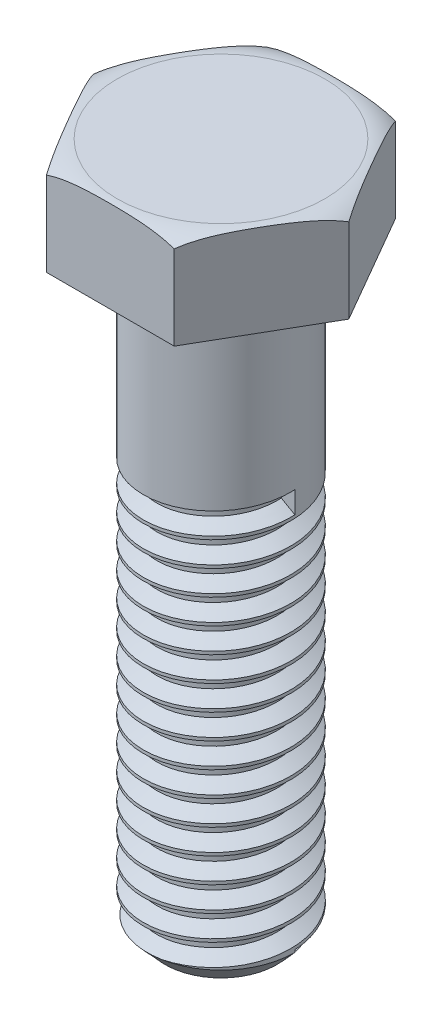
SolidWorks part; units mm, degrees
ref_plane "Front Plane" through (0, 0, 0) normal (0, 0, 1) x (1, 0, 0)
ref_plane "Top Plane" through (0, 0, 0) normal (0, 1, 0) x (1, 0, 0)
ref_plane "Right Plane" through (0, 0, 0) normal (1, 0, 0) x (0, 0, -1)
sketch "Sketch1" plane through (0, 0, 0) normal (0, 1, 0) x (1, 0, 0)
  line L1 (8.1462, 0) -> (4.0731, 7.0549)
  line L2 (4.0731, 7.0549) -> (-4.0731, 7.0548)
  line L3 (-4.0731, 7.0548) -> (-8.1462, 0)
  line L4 (-8.1462, 0) -> (-4.0731, -7.0549)
  line L5 (-4.0731, -7.0549) -> (4.0731, -7.0548)
  line L6 (4.0731, -7.0548) -> (8.1462, 0)
  circle A0 centre (0, 0) radius 7.0549 construction
  dimension "D1" = 14.1097
extrude "Boss-Extrude1" add sketch "Sketch1" against normal blind 43.8023
sketch "Sketch2" plane through (0, -43.8023, 0) normal (0, -1, 0) x (1, 0, 0)
  line L0 (-8.1462, 0) -> (-4.0731, 7.0549) construction
  line L1 (-8.1462, 0) -> (-4.0731, 7.0549)
  line L2 (-4.0731, -7.0548) -> (-8.1462, 0) construction
  line L3 (4.0731, -7.0549) -> (-4.0731, -7.0548) construction
  line L4 (8.1462, 0) -> (4.0731, -7.0549) construction
  line L5 (4.0731, 7.0548) -> (8.1462, 0) construction
  line L6 (-4.0731, 7.0549) -> (4.0731, 7.0548) construction
  line L7 (-4.0731, -7.0548) -> (-8.1462, 0)
  line L8 (4.0731, -7.0549) -> (-4.0731, -7.0548)
  line L9 (8.1462, 0) -> (4.0731, -7.0549)
  line L10 (4.0731, 7.0548) -> (8.1462, 0)
  line L11 (-4.0731, 7.0549) -> (4.0731, 7.0548)
  circle A0 centre (0, 0) radius 4.7053
  dimension "D1" = 9.4107
extrude "Cut-Extrude1" cut sketch "Sketch2" against normal blind 37.9222
thread "Thread1" pitch 1.5875 method cut profile "Thread Profile1" start angle 0, offset 0, length 25.4, pitch 1.5875, diameter 9.4107
ref_plane "Plane1" through (4.7054, -43.8023, 0) normal (0, 0, 1) x (1, 0, 0)
sketch "Thread Profile1" plane through (4.7054, -43.8023, 0) normal (0, 0, 1) x (1, 0, 0)
  line L0 (0, 0) -> (0, 1.5875) construction
  line L11 (0, 0) -> (0, 1.3891)
  line L12 (0, 1.3891) -> (-0.8593, 0.893)
  line L13 (-0.8593, 0.893) -> (-0.8593, 0.4961)
  line L15 (-0.8593, 0.4961) -> (0, 0)
  line L17 (-0.8593, 0.6945) -> (0, 0.6945) construction
  point P2 (0, 0)
  dimension "Pitch" = 1.5875
  dimension "Profile_Angle" = 60
  dimension "Profile_Land" = 0.3969
  dimension "Profile_Height" = 0.8593
sketch "Sketch8" plane through (0, 0, 0) normal (0, 0, 1) x (1, 0, 0)
  line L0 (-0.1235, -43.8023) -> (8.5552, -43.8023) construction
  line L1 (-4.7054, -43.8023) -> (4.7054, -43.8023) construction
  line L2 (0, -44.3948) -> (0, -41.2226) construction
  line L3 (3.0373, -43.8023) -> (2.8966, -43.6616)
  line L7 (3.5696, -43.8023) -> (5.2966, -41.9236)
  line L8 (5.2966, -41.9236) -> (5.2966, -43.8023)
  line L9 (5.2966, -43.8023) -> (3.5696, -43.8023)
  line L11 (0, -43.6616) -> (0, -43.8023)
  line L12 (0, -43.8023) -> (3.0373, -43.8023)
  line L13 (0, -43.6616) -> (2.8966, -43.6616)
  spline S0 degree 2 poles (4.7054, -42.4132) (4.7054, -42.314) (3.3272, -42.2148) (1.949, -42.1156) (0, -42.0164) (-1.949, -41.9171) (-3.3272, -41.8179) (-4.7054, -41.7187) (-4.7054, -41.6195) (-4.7054, -41.5203) (-3.3272, -41.4211) (-1.949, -41.3218) (0, -41.2226) (1.949, -41.1234) (3.3272, -41.0242) (4.7054, -40.925) (4.7054, -40.8257) (4.7054, -40.7265) (3.3272, -40.6273) (1.949, -40.5281) (0, -40.4289) (-1.949, -40.3296) (-3.3272, -40.2304) (-4.7054, -40.1312) (-4.7054, -40.032) (-4.7054, -39.9328) (-3.3272, -39.8336) (-1.949, -39.7343) (0, -39.6351) (1.949, -39.5359) (3.3272, -39.4367) (4.7054, -39.3375) (4.7054, -39.2382) (4.7054, -39.139) (3.3272, -39.0398) (1.949, -38.9406) (0, -38.8414) (-1.949, -38.7421) (-3.3272, -38.6429) (-4.7054, -38.5437) (-4.7054, -38.4445) (-4.7054, -38.3453) (-3.3272, -38.2461) (-1.949, -38.1468) (0, -38.0476) (1.949, -37.9484) (3.3272, -37.8492) (4.7054, -37.75) (4.7054, -37.6507) (4.7054, -37.5515) (3.3272, -37.4523) (1.949, -37.3531) (0, -37.2539) (-1.949, -37.1546) (-3.3272, -37.0554) (-4.7054, -36.9562) (-4.7054, -36.857) (-4.7054, -36.7578) (-3.3272, -36.6586) (-1.949, -36.5593) (0, -36.4601) (1.949, -36.3609) (3.3272, -36.2617) (4.7054, -36.1625) (4.7054, -36.0632) (4.7054, -35.964) (3.3272, -35.8648) (1.949, -35.7656) (0, -35.6664) (-1.949, -35.5671) (-3.3272, -35.4679) (-4.7054, -35.3687) (-4.7054, -35.2695) (-4.7054, -35.1703) (-3.3272, -35.0711) (-1.949, -34.9718) (0, -34.8726) (1.949, -34.7734) (3.3272, -34.6742) (4.7054, -34.575) (4.7054, -34.4757) (4.7054, -34.3765) (3.3272, -34.2773) (1.949, -34.1781) (0, -34.0789) (-1.949, -33.9796) (-3.3272, -33.8804) (-4.7054, -33.7812) (-4.7054, -33.682) (-4.7054, -33.5828) (-3.3272, -33.4836) (-1.949, -33.3843) (0, -33.2851) (1.949, -33.1859) (3.3272, -33.0867) (4.7054, -32.9875) (4.7054, -32.8882) (4.7054, -32.789) (3.3272, -32.6898) (1.949, -32.5906) (0, -32.4914) (-1.949, -32.3921) (-3.3272, -32.2929) (-4.7054, -32.1937) (-4.7054, -32.0945) (-4.7054, -31.9953) (-3.3272, -31.8961) (-1.949, -31.7968) (0, -31.6976) (1.949, -31.5984) (3.3272, -31.4992) (4.7054, -31.4) (4.7054, -31.3007) (4.7054, -31.2015) (3.3272, -31.1023) (1.949, -31.0031) (0, -30.9039) (-1.949, -30.8046) (-3.3272, -30.7054) (-4.7054, -30.6062) (-4.7054, -30.507) (-4.7054, -30.4078) (-3.3272, -30.3086) (-1.949, -30.2093) (0, -30.1101) (1.949, -30.0109) (3.3272, -29.9117) (4.7054, -29.8125) (4.7054, -29.7132) (4.7054, -29.614) (3.3272, -29.5148) (1.949, -29.4156) (0, -29.3164) (-1.949, -29.2171) (-3.3272, -29.1179) (-4.7054, -29.0187) (-4.7054, -28.9195) (-4.7054, -28.8203) (-3.3272, -28.7211) (-1.949, -28.6218) (0, -28.5226) (1.949, -28.4234) (3.3272, -28.3242) (4.7054, -28.225) (4.7054, -28.1257) (4.7054, -28.0265) (3.3272, -27.9273) (1.949, -27.8281) (0, -27.7289) (-1.949, -27.6296) (-3.3272, -27.5304) (-4.7054, -27.4312) (-4.7054, -27.332) (-4.7054, -27.2328) (-3.3272, -27.1336) (-1.949, -27.0343) (0, -26.9351) (1.949, -26.8359) (3.3272, -26.7367) (4.7054, -26.6375) (4.7054, -26.5382) (4.7054, -26.439) (3.3272, -26.3398) (1.949, -26.2406) (0, -26.1414) (-1.949, -26.0421) (-3.3272, -25.9429) (-4.7054, -25.8437) (-4.7054, -25.7445) (-4.7054, -25.6453) (-3.3272, -25.5461) (-1.949, -25.4468) (0, -25.3476) (1.949, -25.2484) (3.3272, -25.1492) (4.7054, -25.05) (4.7054, -24.9507) (4.7054, -24.8515) (3.3272, -24.7523) (1.949, -24.6531) (0, -24.5539) (-1.949, -24.4546) (-3.3272, -24.3554) (-4.7054, -24.2562) (-4.7054, -24.157) (-4.7054, -24.0578) (-3.3272, -23.9586) (-1.949, -23.8593) (0, -23.7601) (1.949, -23.6609) (3.3272, -23.5617) (4.7054, -23.4625) (4.7054, -23.3632) (4.7054, -23.264) (3.3272, -23.1648) (1.949, -23.0656) (0, -22.9664) (-1.949, -22.8671) (-3.3272, -22.7679) (-4.7054, -22.6687) (-4.7054, -22.5695) (-4.7054, -22.4703) (-3.3272, -22.3711) (-1.949, -22.2718) (0, -22.1726) (1.949, -22.0734) (3.3272, -21.9742) (4.7054, -21.875) (4.7054, -21.7757) (4.7054, -21.6765) (3.3272, -21.5773) (1.949, -21.4781) (0, -21.3789) (-1.949, -21.2796) (-3.3272, -21.1804) (-4.7054, -21.0812) (-4.7054, -20.982) (-4.7054, -20.8828) (-3.3272, -20.7836) (-1.949, -20.6843) (0, -20.5851) (1.949, -20.4859) (3.3272, -20.3867) (4.7054, -20.2875) (4.7054, -20.1882) (4.7054, -20.089) (3.3272, -19.9898) (1.949, -19.8906) (0, -19.7914) (-1.949, -19.6921) (-3.3272, -19.5929) (-4.7054, -19.4937) (-4.7054, -19.3945) (-4.7054, -19.2953) (-3.3272, -19.1961) (-1.949, -19.0968) (0, -18.9976) (1.949, -18.8984) (3.3272, -18.7992) (4.7054, -18.7) (4.7054, -18.6007) (4.7054, -18.5015) (3.3272, -18.4023) (1.949, -18.3031) (0, -18.2039) (-1.949, -18.1046) (-3.3272, -18.0054) (-4.7054, -17.9062) (-4.7054, -17.807) (-4.7054, -17.7078) (-3.3272, -17.6086) (-1.949, -17.5093) (0, -17.4101) (1.949, -17.3109) (3.3272, -17.2117) (4.7054, -17.1125) (4.7054, -17.0132) knots 0 0 0 0.007812 0.007812 0.015625 0.015625 0.023438 0.023438 0.03125 0.03125 0.039062 0.039062 0.046875 0.046875 0.054688 0.054688 0.0625 0.0625 0.070312 0.070312 0.078125 0.078125 0.085938 0.085938 0.09375 0.09375 0.101562 0.101562 0.109375 0.109375 0.117188 0.117188 0.125 0.125 0.132812 0.132812 0.140625 0.140625 0.148438 0.148438 0.15625 0.15625 0.164062 0.164062 0.171875 0.171875 0.179688 0.179688 0.1875 0.1875 0.195312 0.195312 0.203125 0.203125 0.210938 0.210938 0.21875 0.21875 0.226562 0.226562 0.234375 0.234375 0.242188 0.242188 0.25 0.25 0.257812 0.257812 0.265625 0.265625 0.273438 0.273438 0.28125 0.28125 0.289062 0.289062 0.296875 0.296875 0.304688 0.304688 0.3125 0.3125 0.320312 0.320312 0.328125 0.328125 0.335938 0.335938 0.34375 0.34375 0.351562 0.351562 0.359375 0.359375 0.367188 0.367188 0.375 0.375 0.382812 0.382812 0.390625 0.390625 0.398438 0.398438 0.40625 0.40625 0.414062 0.414062 0.421875 0.421875 0.429688 0.429688 0.4375 0.4375 0.445312 0.445312 0.453125 0.453125 0.460938 0.460938 0.46875 0.46875 0.476562 0.476562 0.484375 0.484375 0.492188 0.492188 0.5 0.5 0.507812 0.507812 0.515625 0.515625 0.523438 0.523438 0.53125 0.53125 0.539062 0.539062 0.546875 0.546875 0.554688 0.554688 0.5625 0.5625 0.570312 0.570312 0.578125 0.578125 0.585938 0.585938 0.59375 0.59375 0.601562 0.601562 0.609375 0.609375 0.617188 0.617188 0.625 0.625 0.632812 0.632812 0.640625 0.640625 0.648438 0.648438 0.65625 0.65625 0.664062 0.664062 0.671875 0.671875 0.679688 0.679688 0.6875 0.6875 0.695312 0.695312 0.703125 0.703125 0.710938 0.710938 0.71875 0.71875 0.726562 0.726562 0.734375 0.734375 0.742188 0.742188 0.75 0.75 0.757812 0.757812 0.765625 0.765625 0.773438 0.773438 0.78125 0.78125 0.789062 0.789062 0.796875 0.796875 0.804688 0.804688 0.8125 0.8125 0.820312 0.820312 0.828125 0.828125 0.835938 0.835938 0.84375 0.84375 0.851562 0.851562 0.859375 0.859375 0.867188 0.867188 0.875 0.875 0.882812 0.882812 0.890625 0.890625 0.898438 0.898438 0.90625 0.90625 0.914062 0.914062 0.921875 0.921875 0.929688 0.929688 0.9375 0.9375 0.945312 0.945312 0.953125 0.953125 0.960938 0.960938 0.96875 0.96875 0.976562 0.976562 0.984375 0.984375 0.992188 0.992188 1 1 1 weights 1 0.92388 1 0.92388 1 0.92388 1 0.92388 1 0.92388 1 0.92388 1 0.92388 1 0.92388 1 0.92388 1 0.92388 1 0.92388 1 0.92388 1 0.92388 1 0.92388 1 0.92388 1 0.92388 1 0.92388 1 0.92388 1 0.92388 1 0.92388 1 0.92388 1 0.92388 1 0.92388 1 0.92388 1 0.92388 1 0.92388 1 0.92388 1 0.92388 1 0.92388 1 0.92388 1 0.92388 1 0.92388 1 0.92388 1 0.92388 1 0.92388 1 0.92388 1 0.92388 1 0.92388 1 0.92388 1 0.92388 1 0.92388 1 0.92388 1 0.92388 1 0.92388 1 0.92388 1 0.92388 1 0.92388 1 0.92388 1 0.92388 1 0.92388 1 0.92388 1 0.92388 1 0.92388 1 0.92388 1 0.92388 1 0.92388 1 0.92388 1 0.92388 1 0.92388 1 0.92388 1 0.92388 1 0.92388 1 0.92388 1 0.92388 1 0.92388 1 0.92388 1 0.92388 1 0.92388 1 0.92388 1 0.92388 1 0.92388 1 0.92388 1 0.92388 1 0.92388 1 0.92388 1 0.92388 1 0.92388 1 0.92388 1 0.92388 1 0.92388 1 0.92388 1 0.92388 1 0.92388 1 0.92388 1 0.92388 1 0.92388 1 0.92388 1 0.92388 1 0.92388 1 0.92388 1 0.92388 1 0.92388 1 0.92388 1 0.92388 1 0.92388 1 0.92388 1 0.92388 1 0.92388 1 0.92388 1 0.92388 1 0.92388 1 0.92388 1 0.92388 1 0.92388 1 0.92388 1 0.92388 1 0.92388 1 0.92388 1 0.92388 1 0.92388 1 0.92388 1 0.92388 1 0.92388 1 0.92388 1 0.92388 1 0.92388 1 0.92388 1 0.92388 1 0.92388 1 0.92388 1 0.92388 1 0.92388 1 0.92388 1 0.92388 1 0.92388 1 0.92388 1 0.92388 1 0.92388 1 construction
revolve "Cut-Revolve2" cut sketch "Sketch8" angle 360 about L2
sketch "Sketch9" plane through (0, 0, 0) normal (0, 0, 1) x (1, 0, 0)
  line L0 (6.6222, 0) -> (8.1462, 0)
  line L1 (4.0731, 0) -> (8.1462, 0) construction
  line L2 (8.1462, 0) -> (8.1462, -0.508)
  line L3 (8.1462, -5.8801) -> (8.1462, 0) construction
  line L4 (0, 2.5645) -> (0, 0.8352) construction
  arc A2 (6.6222, 0) -> (8.1462, -0.508) centre (6.5184, -2.8514) cw
  dimension "D1" = 1.524
  dimension "D2" = 0.508
revolve "Cut-Revolve4" cut sketch "Sketch9" angle 360 about L4
